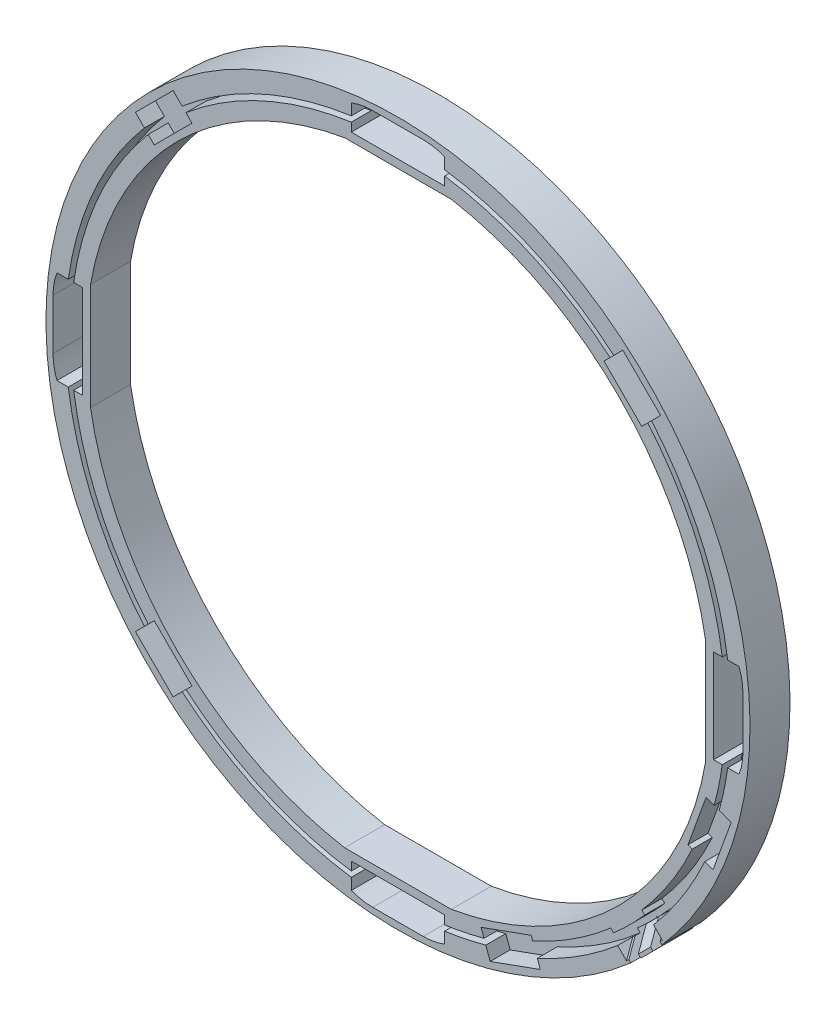
SolidWorks part; units mm, degrees
ref_plane "Front Plane" through (0, 0, 0) normal (0, 0, 1) x (1, 0, 0)
ref_plane "Top Plane" through (0, 0, 0) normal (0, 1, 0) x (1, 0, 0)
ref_plane "Right Plane" through (0, 0, 0) normal (1, 0, 0) x (0, 0, -1)
sketch "Sketch2" plane through (0, 0, 0) normal (0, 0, 1) x (1, 0, 0)
  line L0 (0, 0) -> (0, 31.8027) construction
  line L1 (-4, 23.0556) -> (4, 23.0556)
  line L2 (23.0556, 4) -> (23.0556, -4)
  line L3 (4, -23.0556) -> (-4, -23.0556)
  line L4 (-23.0556, -4) -> (-23.0556, 4)
  circle A0 centre (0, 0) radius 26.4
  arc A1 (-4, 23.0556) -> (-23.0556, 4) centre (0, 0) ccw
  arc A2 (4, 23.0556) -> (0, 23.4) centre (0, 0) ccw construction
  arc A3 (0, 23.4) -> (-4, 23.0556) centre (0, 0) ccw construction
  arc A4 (23.0556, -4) -> (23.0556, 4) centre (0, 0) ccw construction
  arc A5 (23.0556, 4) -> (4, 23.0556) centre (0, 0) ccw
  arc A6 (-4, -23.0556) -> (4, -23.0556) centre (0, 0) ccw construction
  arc A7 (4, -23.0556) -> (23.0556, -4) centre (0, 0) ccw
  arc A8 (-23.0556, 4) -> (-23.0556, -4) centre (0, 0) ccw construction
  arc A9 (-23.0556, -4) -> (-4, -23.0556) centre (0, 0) ccw
  dimension "D1" = 52.8
  dimension "D4" = 4
extrude "Extrude1" add sketch "Sketch2" along normal blind 3
ref_plane "Plane1" through (0, 0, 3) normal (0, 0, 1) x (1, 0, 0)
sketch "Sketch4" plane through (0, 0, 0) normal (1, 0, 0) x (0, 0, -1)
  line L0 (-3, 26.4) -> (-3.3, 23.1028)
  line L1 (-3.3, 23.1028) -> (-3.3, 0)
  line L2 (0, 0) -> (-3, 0) construction
  line L3 (-3, 26.4) -> (-3, -26.4) construction
  line L4 (-3.3, 0) -> (-3, 0)
  line L5 (-3, 0) -> (-3, 26.4)
  dimension "D1" = 0.3
revolve "Cut-Revolve1" [suppressed] cut sketch "Sketch4" angle 360 about L2
sketch "Sketch3" plane through (0, 0, 3) normal (0, 0, 1) x (1, 0, 0)
  line L0 (0, 0) -> (0, 29.437) construction
  line L1 (0, 0) -> (35.1715, 0) construction
  line L2 (-1.8939, 25.8711) -> (1.8939, 25.8711)
  line L3 (3.5, 25.5741) -> (3.5, 23.6711)
  line L4 (3.5, 23.6711) -> (-3.5, 23.6711)
  line L5 (1.8939, 25.8711) -> (3.5, 25.8711) construction
  line L6 (3.5, 25.8711) -> (3.5, 25.5741) construction
  line L7 (-3.5, 25.8711) -> (-3.5, 25.5741) construction
  line L8 (-1.8939, 25.8711) -> (-3.5, 25.8711) construction
  line L9 (-3.5, 25.5741) -> (-3.5, 23.6711)
  line L10 (23.6711, -3.5) -> (23.6711, 3.5)
  line L11 (25.5741, 3.5) -> (23.6711, 3.5)
  line L12 (25.8711, 1.8939) -> (25.8711, -1.8939)
  line L13 (25.5741, -3.5) -> (23.6711, -3.5)
  line L14 (-3.5, -23.6711) -> (3.5, -23.6711)
  line L15 (3.5, -25.5741) -> (3.5, -23.6711)
  line L16 (1.8939, -25.8711) -> (-1.8939, -25.8711)
  line L17 (-3.5, -25.5741) -> (-3.5, -23.6711)
  line L18 (-23.6711, 3.5) -> (-23.6711, -3.5)
  line L19 (-25.5741, -3.5) -> (-23.6711, -3.5)
  line L20 (-25.8711, -1.8939) -> (-25.8711, 1.8939)
  line L21 (-25.5741, 3.5) -> (-23.6711, 3.5)
  arc A0 (1.8939, 25.8711) -> (3.5, 25.5741) centre (1.8939, 21.3807) cw
  arc A1 (-1.8939, 25.8711) -> (-3.5, 25.5741) centre (-1.8939, 21.3807) ccw
  arc A2 (25.8711, 1.8939) -> (25.5741, 3.5) centre (21.3807, 1.8939) ccw
  arc A3 (25.8711, -1.8939) -> (25.5741, -3.5) centre (21.3807, -1.8939) cw
  arc A4 (1.8939, -25.8711) -> (3.5, -25.5741) centre (1.8939, -21.3807) ccw
  arc A5 (-1.8939, -25.8711) -> (-3.5, -25.5741) centre (-1.8939, -21.3807) cw
  arc A6 (-25.8711, -1.8939) -> (-25.5741, -3.5) centre (-21.3807, -1.8939) ccw
  arc A7 (-25.8711, 1.8939) -> (-25.5741, 3.5) centre (-21.3807, 1.8939) cw
  point P12 (0, 23.6711)
  point P13 (0, 25.8711)
  dimension "D1" = 2.2
  dimension "D2" = 7
  dimension "D3" = 4
extrude "Extrude2" cut sketch "Sketch3" against normal blind 3
sketch "Sketch5" plane through (0, 0, 3) normal (0, 0, 1) x (1, 0, 0)
  line L0 (0, 23.6711) -> (0, 25.8711) construction
  line L3 (1.8939, 25.8711) -> (-1.8939, 25.8711) construction
  line L4 (-3.5, 23.6711) -> (3.5, 23.6711) construction
  circle A0 centre (0, 0) radius 24.7711 construction
  circle A1 centre (0, 0) radius 24.5711
  circle A2 centre (0, 0) radius 24.9711
  point P9 (0, 24.7711)
  dimension "D1" = 0.2
  dimension "D2" = 0.2
extrude "Extrude3" cut sketch "Sketch5" against normal blind 1.5
sketch "Sketch8" plane through (0, 0, 3) normal (0, 0, 1) x (1, 0, 0)
  line L0 (0, 0) -> (22.1886, -22.1886) construction
  line L1 (0, 0) -> (20.1949, 0) construction
  line L2 (18.2822, -17.0094) -> (16.5335, -15.2607)
  line L3 (16.5335, -15.2607) -> (17.2395, -14.5547)
  line L4 (17.2395, -14.5547) -> (18.9486, -16.2638)
  line L5 (18.9486, -16.2638) -> (18.2822, -17.0094)
  line L6 (14.5547, -17.2395) -> (16.2638, -18.9486)
  line L7 (15.2607, -16.5335) -> (14.5547, -17.2395)
  line L8 (17.0094, -18.2822) -> (15.2607, -16.5335)
  line L9 (16.2638, -18.9486) -> (17.0094, -18.2822)
  arc A1 (3.5, -24.7246) -> (24.7246, -3.5) centre (0, 0) ccw construction
  dimension "D1" = 45
  dimension "D2" = 1
  dimension "D3" = 1.8
extrude "Extrude5" [suppressed] cut sketch "Sketch8" against normal blind 5
sketch "Sketch6" plane through (0, 0, 3) normal (0, 0, 1) x (1, 0, 0)
  line L0 (0, 0) -> (21.6921, 21.6921) construction
  line L1 (0, 0) -> (0, 29.7187) construction
  line L2 (0, 0) -> (-21.6921, 21.6921) construction
  line L3 (16.8628, 19.6912) -> (19.6912, 16.8628)
  line L4 (19.6912, 16.8628) -> (18.277, 15.4486)
  line L5 (18.277, 15.4486) -> (15.4486, 18.277)
  line L6 (17.6573, 17.6573) -> (17.3744, 17.3744) construction
  line L7 (16.8628, 19.6912) -> (15.4486, 18.277)
  line L8 (-19.6912, 16.8628) -> (-18.277, 15.4486)
  line L9 (-16.8628, 19.6912) -> (-19.6912, 16.8628)
  line L10 (-16.8628, 19.6912) -> (-15.4486, 18.277)
  line L11 (-18.277, 15.4486) -> (-15.4486, 18.277)
  line L12 (0, 0) -> (39.4072, 0) construction
  line L13 (19.6912, -16.8628) -> (18.277, -15.4486)
  line L14 (16.8628, -19.6912) -> (19.6912, -16.8628)
  line L15 (16.8628, -19.6912) -> (15.4486, -18.277)
  line L16 (18.277, -15.4486) -> (15.4486, -18.277)
  line L17 (-16.8628, -19.6912) -> (-19.6912, -16.8628)
  line L18 (-16.8628, -19.6912) -> (-15.4486, -18.277)
  line L19 (-18.277, -15.4486) -> (-15.4486, -18.277)
  line L20 (-19.6912, -16.8628) -> (-18.277, -15.4486)
  line L21 (0, 0) -> (34.2783, 7.6346) construction
  line L22 (24.9865, -6.912) -> (23.1057, -6.2317)
  line L23 (23.6258, -10.6735) -> (24.9865, -6.912)
  line L24 (23.6258, -10.6735) -> (21.745, -9.9931)
  line L25 (23.1057, -6.2317) -> (21.745, -9.9931)
  line L26 (0, 0) -> (11.4166, -11.4166) construction
  line L27 (10.6735, -23.6258) -> (6.912, -24.9865)
  line L28 (10.6735, -23.6258) -> (9.9931, -21.745)
  line L29 (6.2317, -23.1057) -> (9.9931, -21.745)
  line L30 (6.912, -24.9865) -> (6.2317, -23.1057)
  arc A0 (24.7246, 3.5) -> (3.5, 24.7246) centre (0, 0) ccw construction
  point P21 (16.8628, 16.8628)
  point P22 (18.277, 18.277)
  dimension "D1" = 45
  dimension "D2" = 2
  dimension "D3" = 4
extrude "Extrude4" cut sketch "Sketch6" against normal blind 1.5 contours L8 L11 L10 L9 | L3 L7 L5 L4 | L20 L17 L18 L19 | L30 L27 L28 L29 | L22 L25 L24 L23 region at (17.5699, 17.5699, 3) region at (-17.5699, 17.5699, 3) region at (-17.5699, -17.5699, 3) region at (23.3657, -8.4526, 3) region at (8.4526, -23.3657, 3)
ref_plane "Plane3" through (0, 0, 0) normal (0.7071, 0.7071, 0) x (0.7071, -0.7071, 0)
sketch "Sketch13" plane through (0, 0, 3) normal (0, 0, 1) x (1, 0, 0)
  line L0 (0, 0) -> (25.3776, -25.3776) construction
  line L1 (0, 0) -> (11.536, 0) construction
  line L2 (18.1109, -17.1917) -> (19.4443, -18.5251)
  line L3 (19.4443, -18.5251) -> (20.1514, -17.8179)
  line L4 (20.1514, -17.8179) -> (18.7854, -16.452)
  line L5 (18.7854, -16.452) -> (18.1109, -17.1917)
  line L6 (17.8179, -20.1514) -> (16.452, -18.7854)
  line L7 (18.5251, -19.4443) -> (17.8179, -20.1514)
  line L8 (17.1917, -18.1109) -> (18.5251, -19.4443)
  line L9 (16.452, -18.7854) -> (17.1917, -18.1109)
  arc A0 (3.5, -24.7246) -> (6.5866, -24.0868) centre (0, 0) ccw construction
  dimension "D1" = 45
  dimension "D2" = 1.3
  dimension "D3" = 1
extrude "Extrude11" cut sketch "Sketch13" against normal blind 3.8
sketch "Sketch14" plane through (0, 0, 3) normal (0, 0, 1) x (1, 0, 0)
  line L0 (3.5, -24.3206) -> (3.5, -24.7246) construction
  line L1 (10.4504, -23.0091) -> (10.2798, -22.5374)
  line L2 (10.6735, -23.6258) -> (10.348, -22.7261) construction
  line L3 (16.452, -18.7854) -> (17.4644, -19.7978) construction
  line L4 (10.2798, -22.5374) -> (10.1091, -22.0657)
  line L5 (10.2115, -22.3487) -> (9.9931, -21.745) construction
  line L6 (16.6645, -18.998) -> (15.9559, -18.2893)
  line L7 (0, 0) -> (10.8066, -10.8066) construction
  line L8 (23.0091, -10.4504) -> (22.5374, -10.2798)
  line L9 (22.5374, -10.2798) -> (22.0657, -10.1091)
  line L10 (18.998, -16.6645) -> (18.2893, -15.9559)
  circle A0 centre (0, 0) radius 24.7711 construction
  arc A1 (10.4504, -23.0091) -> (16.6645, -18.998) centre (0, 0) ccw
  arc A2 (10.1091, -22.0657) -> (15.9559, -18.2893) centre (0, 0) ccw
  arc A3 (23.0091, -10.4504) -> (18.998, -16.6645) centre (0, 0) cw
  arc A4 (22.0657, -10.1091) -> (18.2893, -15.9559) centre (0, 0) cw
  point P0 (3.5, -24.5226)
  dimension "D1" = 0.5
  dimension "D2" = 0.5
extrude "Extrude12" cut sketch "Sketch14" against normal up to surface (1.5 mm away) up to face at (-16.5614, 16.5614, 1.5)
sketch "Sketch12" plane through (0, 0, 0) normal (0.7071, 0.7071, 0) x (0.7071, -0.7071, 0)
  line L0 (24.8952, -1.4993) -> (26.3085, -3.1963)
  line L1 (26.3085, -3.1963) -> (24.7674, -3.1963)
  line L2 (24.7674, -3.1963) -> (24.8952, -1.4993)
extrude "Extrude10" cut sketch "Sketch12" against normal mid plane 3.8
